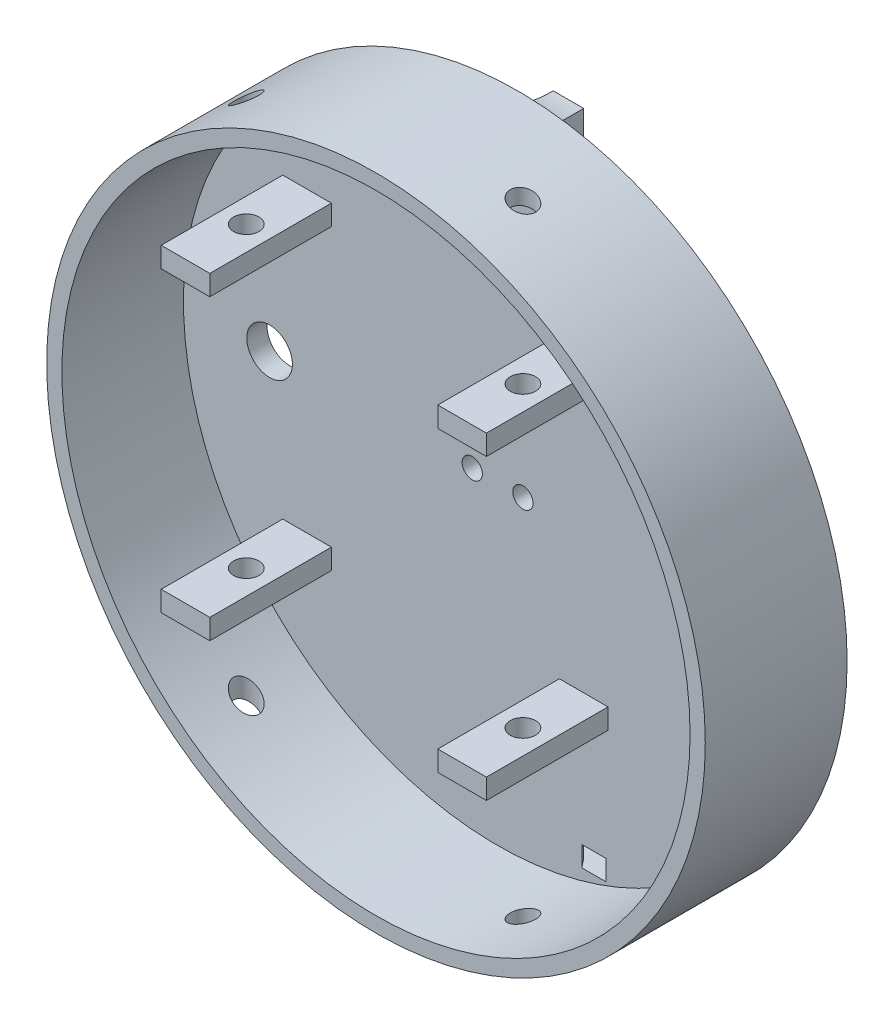
SolidWorks part; units mm, degrees
ref_plane "Alzado" through (0, 0, 0) normal (0, 0, 1) x (1, 0, 0)
ref_plane "Planta" through (0, 0, 0) normal (0, 1, 0) x (1, 0, 0)
ref_plane "Vista lateral" through (0, 0, 0) normal (1, 0, 0) x (0, 0, -1)
sketch "Croquis1" plane through (0, 0, 0) normal (0, 0, 1) x (1, 0, 0)
  line L0 (10, 20) -> (-10, 20) construction
  circle A0 centre (0, 0) radius 32.5
  circle A1 centre (-2.5, 0) radius 1
  circle A2 centre (2.5, 0) radius 1
  circle A3 centre (0, 20) radius 1
  circle A4 centre (10, 20) radius 1
  circle A5 centre (-10, 20) radius 1
  point P9 (0, 20)
  dimension "D1" = 65
  dimension "D4" = 2
  dimension "D7" = 2
  dimension "D2" = 2.5
  dimension "D3" = 2.5
  dimension "D5" = 20
  dimension "D6" = 20
extrude "Saliente-Extruir1" add sketch "Croquis1" along normal blind 2
sketch "Croquis2" plane through (0, 0, 2) normal (0, 0, 1) x (1, 0, 0)
  line L0 (-21.2, -15.7) -> (-16.4, -15.7)
  line L1 (10.9, -15.7) -> (6.1, -15.7)
  line L2 (-21.2, -15.7) -> (-21.2, -13.7)
  line L3 (-21.2, -13.7) -> (-16.4, -13.7)
  line L4 (-16.4, -13.7) -> (-16.4, -15.7)
  line L5 (6.1, -15.7) -> (6.1, -13.7)
  line L6 (6.1, -13.7) -> (10.9, -13.7)
  line L7 (10.9, -13.7) -> (10.9, -15.7)
  line L8 (6.1, -15.7) -> (10.9, -15.7)
  line L9 (0, 0) -> (12.8027, 0) construction
  line L10 (10.9, 13.7) -> (10.9, 15.7)
  line L11 (10.9, 15.7) -> (6.1, 15.7)
  line L12 (6.1, 13.7) -> (10.9, 13.7)
  line L13 (6.1, 15.7) -> (6.1, 13.7)
  line L14 (-16.4, 13.7) -> (-16.4, 15.7)
  line L15 (-21.2, 15.7) -> (-16.4, 15.7)
  line L16 (-21.2, 15.7) -> (-21.2, 13.7)
  line L17 (-21.2, 13.7) -> (-16.4, 13.7)
  point P2 (0, -15.7)
  point P3 (-16.4, -15.7)
  point P13 (8.5, -15.7)
  point P16 (8.5, 15.7)
  dimension "D1" = 32.1
  dimension "D2" = 10.9
  dimension "D3" = 15.7
  dimension "D4" = 4.8
  dimension "D5" = 4.8
  dimension "D6" = 2
  dimension "D7" = 2
extrude "Saliente-Extruir2" add sketch "Croquis2" along normal blind 12 contours L7 L6 L5 L1 | L4 L3 L2 L0 | L16 L17 L14 L15 | L11 L13 L12 L10 region at (-18.8, -14.7, 2) region at (8.5, -14.7, 2) region at (8.5, 14.7, 2) region at (-18.8, 14.7, 2)
sketch "Croquis3" plane through (0, -15.7, 0) normal (0, -1, 0) x (1, 0, 0)
  line L0 (-18.8, 14) -> (-18.8, 2) construction
  line L1 (-21.2, 14) -> (-16.4, 14) construction
  line L2 (-21.2, 2) -> (-16.4, 2) construction
  line L3 (8.5, 14) -> (8.5, 2) construction
  line L4 (10.9, 14) -> (6.1, 14) construction
  line L5 (10.9, 2) -> (6.1, 2) construction
  circle A0 centre (-18.8, 8) radius 1.25
  circle A1 centre (8.5, 8) radius 1.25
  dimension "D1" = 2.5
extrude "Cortar-Extruir1" cut sketch "Croquis3" against normal up to surface (31.4 mm away) up to face at (8.5, 15.7, 8)
ref_plane "Plano1" through (0, -32.5, 0) normal (0, -1, 0) x (-1, 0, 0)
ref_plane "Plano2" through (0, -28.75, 0) normal (0, -1, 0) x (-1, 0, 0)
sketch "Croquis5" plane through (0, -28.75, 0) normal (0, -1, 0) x (-1, 0, 0)
  line L0 (-8.5, -8) -> (18.8, -8) construction
  line L1 (0, 0) -> (0, -8) construction
  line L2 (-32.5, -2) -> (32.5, -2) construction
  line L3 (-10.68, -2) -> (-8.3104, -2)
  line L4 (32.5, 0) -> (-32.5, 0) construction
  line L5 (9.277, 0) -> (6.408, 0)
  line L6 (8.3104, -2) -> (10.68, -2)
  line L7 (-6.408, 0) -> (-9.277, 0)
  arc A0 (-9.277, 0) -> (-10.68, -2) centre (0, -8) ccw
  arc A1 (-6.408, 0) -> (-8.3104, -2) centre (0, -8) ccw
  arc A2 (10.68, -2) -> (9.277, 0) centre (0, -8) ccw
  arc A3 (8.3104, -2) -> (6.408, 0) centre (0, -8) ccw
  dimension "D1" = 24.5
  dimension "D2" = 20.5
extrude "Cortar-Extruir3" cut sketch "Croquis5" against normal blind 2
mirror "Simetría1" about plane through (0, 0, 0) normal (0, 1, 0) of "Cortar-Extruir3"
sketch "Croquis6" plane through (0, 0, 0) normal (0, 0, -1) x (-1, 0, 0)
  circle A0 centre (-22.5, 12.5) radius 2.25
  circle A1 centre (-22.5, -12.5) radius 2.25
  circle A2 centre (22.5, 0) radius 2.25
  point P0 (0, 0)
  point P8 (0, 0)
  dimension "D1" = 4.5
  dimension "D2" = 4.5
  dimension "D3" = 4.5
  dimension "D4" = 45
  dimension "D5" = 22.5
  dimension "D6" = 25
  dimension "D7" = 12.5
extrude "Cortar-Extruir4" cut sketch "Croquis6" against normal blind 2.5
sketch "Croquis7" plane through (0, 0, 2) normal (0, 0, 1) x (1, 0, 0)
  circle A2 centre (0, 0) radius 32.5 construction
  circle A9 centre (0, 0) radius 32.5
  circle A11 centre (0, 0) radius 31
  dimension "D1" = 1.5
extrude "Saliente-Extruir3" add sketch "Croquis7" along normal blind 12
ref_plane "Plano3" through (0, -32.5, 0) normal (0, -1, 0) x (-1, 0, 0)
sketch "Croquis8" plane through (0, -32.5, 0) normal (0, -1, 0) x (-1, 0, 0)
  circle A0 centre (-8.5, -8) radius 1.25 construction
  circle A1 centre (-8.5, -8) radius 1.25
  circle A2 centre (18.8, -8) radius 1.25 construction
  circle A3 centre (18.8, -8) radius 1.25
extrude "Cortar-Extruir5" cut sketch "Croquis8" against normal blind 70
sketch "Sketch1" plane through (0, 0, 0) normal (0, 0, -1) x (-1, 0, 0)
  line L0 (6.408, 26.75) -> (6.408, 28.75) construction
  line L1 (-1.502, 29.25) -> (1.498, 29.25)
  line L2 (-1.502, 29.25) -> (-1.502, 26.25)
  line L3 (-1.502, 26.25) -> (1.498, 26.25)
  line L4 (1.498, 29.25) -> (1.498, 26.25)
  line L5 (-1.502, 29.25) -> (1.498, 26.25) construction
  line L6 (-1.502, 26.25) -> (1.498, 29.25) construction
  line L7 (0, 0) -> (-11.4103, 0) construction
  line L8 (-1.502, -26.25) -> (1.498, -29.25) construction
  line L9 (-1.502, -29.25) -> (1.498, -26.25) construction
  line L10 (1.498, -29.25) -> (1.498, -26.25)
  line L11 (-1.502, -26.25) -> (1.498, -26.25)
  line L12 (-1.502, -29.25) -> (-1.502, -26.25)
  line L13 (-1.502, -29.25) -> (1.498, -29.25)
  line L14 (-6.408, -26.75) -> (-6.408, -28.75) construction
  point P0 (-0.002, 27.75)
  point P8 (6.408, 27.75)
  point P15 (-0.002, -27.75)
  dimension "D1" = 4.91
  dimension "D2" = 3
  dimension "D3" = 3
  dimension "D4" = 4.906
extrude "Boss-Extrude1" add sketch "Sketch1" along normal blind 5
fillet "Fillet1" radius 2 6 edges at (1.502, 27.75, 0) (-1.498, -27.75, 0) (0.002, 26.25, 0) (0.002, 29.25, 0) (0.002, -26.25, 0) (0.002, -29.25, 0) second distance 5 first distance on face at (0.002, 27.75, 0)
sketch "Sketch2" plane through (0, 0, 2) normal (0, 0, 1) x (1, 0, 0)
  line L1 (-10.68, -26.75) -> (-5.6668, -26.75)
  line L2 (-10.68, -26.75) -> (-10.68, -28.75)
  line L3 (-10.68, -28.75) -> (-5.6668, -28.75)
  line L4 (-5.6668, -26.75) -> (-5.6668, -28.75)
  line L5 (10.68, 26.75) -> (5.4941, 26.75)
  line L6 (10.68, 26.75) -> (10.68, 28.75)
  line L7 (10.68, 28.75) -> (5.4941, 28.75)
  line L8 (5.4941, 26.75) -> (5.4941, 28.75)
extrude "Tapon" add sketch "Sketch2" against normal up to surface (2 mm away) up to face at (1.002, 26, 0)
equation "\"D2@Croquis6\"=\"D1@Croquis6\""
equation "\"D3@Croquis6\"=\"D1@Croquis6\""
equation "\"D5@Croquis6\"=\"D4@Croquis6\"/2"
equation "\"D7@Croquis6\"=\"D6@Croquis6\"/2"
